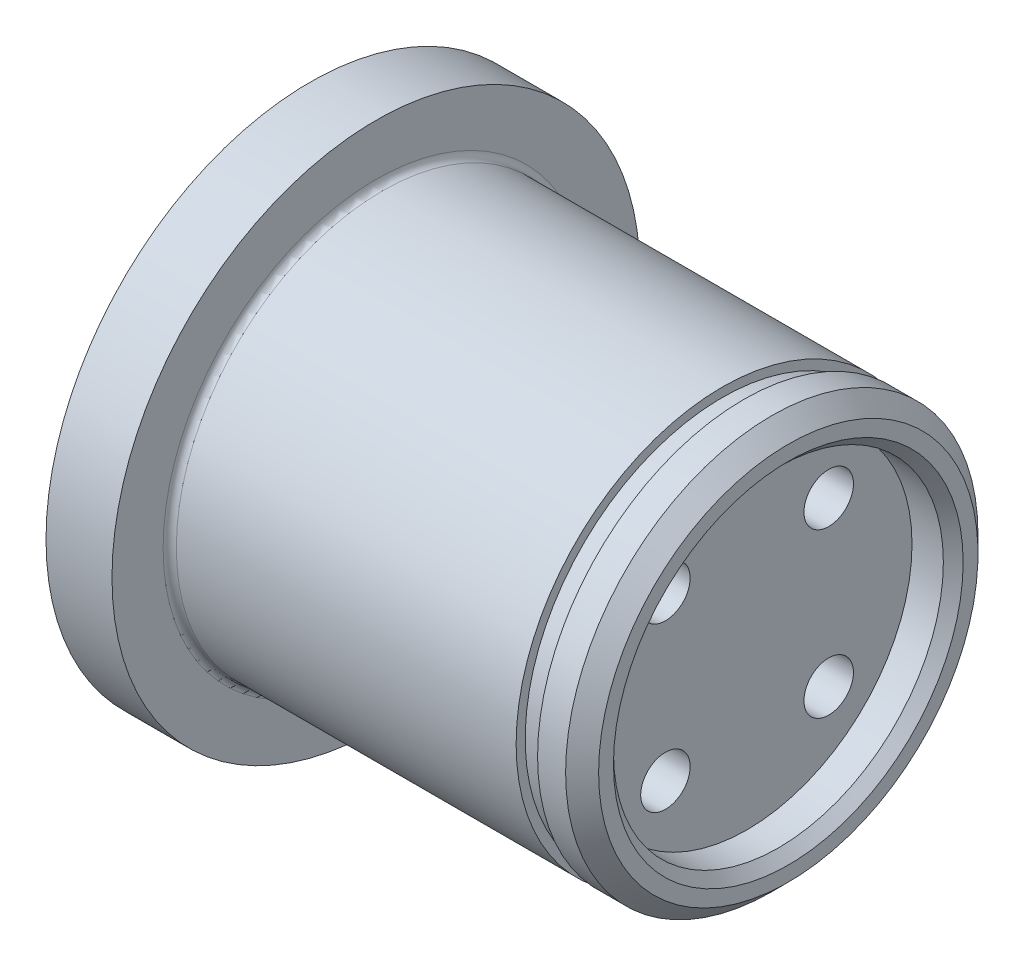
SolidWorks part; units mm, degrees
material "1060 Сплав"
ref_plane "Спереди" through (0, 0, 0) normal (0, 0, 1) x (1, 0, 0)
ref_plane "Сверху" through (0, 0, 0) normal (0, 1, 0) x (1, 0, 0)
ref_plane "Справа" through (0, 0, 0) normal (1, 0, 0) x (0, 0, -1)
sketch "Эскиз1" plane through (0, 0, 0) normal (0, 0, 1) x (1, 0, 0)
  line L0 (0, 0) -> (22138.4448, 0) construction
  line L1 (0, 0) -> (0, 12.5)
  line L2 (0, 12.5) -> (-25, 12.5)
  line L3 (-25, 12.5) -> (-25, 16)
  line L4 (-25, 16) -> (-29, 16)
  line L5 (-29, 16) -> (-29, 0)
  line L8 (0, 0) -> (-29, 0)
  dimension "D1" = 29
  dimension "D2" = 4
  dimension "D3" = 25
  dimension "D6" = 32
revolve "Повернуть1" add sketch "Эскиз1" angle 360 about L0
sketch "Эскиз2" plane through (0, 0, 0) normal (0, 0, 1) x (1, 0, 0)
  line L0 (-4, 12.5) -> (-4, 11.95)
  line L1 (-4, 12.5) -> (-24.6, 12.5) construction
  line L2 (-4, 11.95) -> (-2.7, 11.95)
  line L3 (-2.7, 11.95) -> (-2.7, 12.5)
  line L4 (-2.7, 12.5) -> (-4, 12.5)
  line L5 (0, -12.5) -> (0, 12.5) construction
  line L6 (0, 0) -> (-50000, 0) construction
  point P10 (-2.7, 12.225)
  point P13 (0, 0)
  dimension "D1" = 4
  dimension "D2" = 1.3
  dimension "D3" = 23.9
revolve "Вырез-Повернуть1" cut sketch "Эскиз2" angle 360 about L6
chamfer "Фаска1" distance 1 angle 45 1 edges at (0, 0, 12.5)
fillet "Скругление1" radius 0.4 1 edges at (-25, 0, 12.5)
hole_wizard "Отверстие1" positions "Эскиз3" profile "Эскиз4" legacy end condition through all
sketch "Эскиз3" plane through (0, 0, 0) normal (1, 0, 0) x (0, 0, -1)
  line L0 (0, 0) -> (0, 7) construction
  line L2 (0, 0) -> (4.9497, 4.9497) construction
  circle A0 centre (0, 0) radius 7 construction
  point P0 (4.9497, 4.9497)
  dimension "D1" = 14
  dimension "D2" = 45
sketch "Эскиз4" plane through (0, 4.9497, -4.9497) normal (0, 1, 0) x (0, 0, -1)
  line L0 (0, 0) -> (0, 29)
  line L1 (0, 29) -> (1.5, 29)
  line L2 (1.5, 29) -> (1.5, 0)
  line L3 (1.5, 0) -> (0, 0)
  line L4 (0, 110) -> (0, -10) construction
  dimension "Диаметр" = 3
  dimension "Глубина" = 29
pattern_circular "Круговой массив1" count 4 over 360 about axis through (0, 0, 0) along (-1, 0, 0) of "Отверстие1"
sketch "Эскиз5" plane through (0, 0, 0) normal (0, 0, 1) x (1, 0, 0)
  line L0 (0, 0) -> (0, 10)
  line L1 (0, -11.5) -> (0, 11.5) construction
  line L7 (0, 10) -> (-2.5, 10)
  line L8 (-2.5, 10) -> (-2.5, 0)
  line L9 (-2.5, 0) -> (0, 0)
  line L10 (0, 0) -> (-50000, 0) construction
  dimension "D1" = 2.5
  dimension "D2" = 20
revolve "Вырез-Повернуть2" cut sketch "Эскиз5" angle 360 about L10
chamfer "Фаска2" distance 0.6 angle 45 1 edges at (0, 0, -10)
